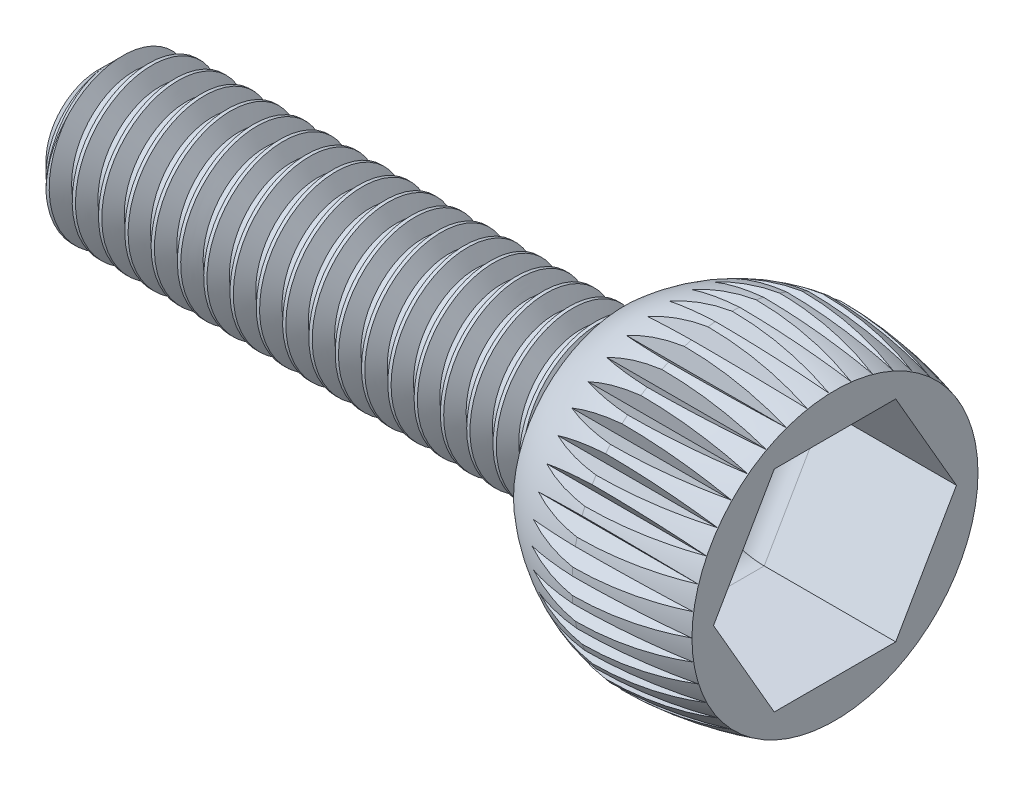
SolidWorks part; units mm, degrees
ref_plane "Front Plane" through (0, 0, 0) normal (0, 0, 1) x (1, 0, 0)
ref_plane "Top Plane" through (0, 0, 0) normal (0, 1, 0) x (1, 0, 0)
ref_plane "Right Plane" through (0, 0, 0) normal (1, 0, 0) x (0, 0, -1)
sketch "Sketch1" plane through (0, 0, 0) normal (1, 0, 0) x (0, 0, -1)
  circle A0 centre (0, 0) radius 3
  dimension "D1" = 6
extrude "Boss-Extrude1" add sketch "Sketch1" along normal blind 20
sketch "Sketch4" plane through (20, 0, 0) normal (1, 0, 0) x (0, 0, -1)
  circle A0 centre (0, 0) radius 6
  dimension "D1" = 12
extrude "Boss-Extrude2" add sketch "Sketch4" along normal blind 8
sketch "Sketch5" plane through (28, 0, 0) normal (1, 0, 0) x (0, 0, -1)
  line L0 (-5.4402, 0) -> (0, 0)
  line L1 (-5.4402, 0) -> (-5.9916, 0.3183)
  line L2 (-6.2799, 0.4848) -> (-6.2799, -0.4848)
  line L3 (-6.2799, -0.4848) -> (-6.2619, -0.4744)
  line L4 (-5.3765, 0.8305) -> (-5.8727, 1.2292)
  line L5 (-6.2803, 0.4795) -> (-6.261, 0.487)
  line L6 (-5.1867, 1.6414) -> (-5.6163, 2.1112)
  line L7 (-6.1335, 1.4326) -> (-6.1132, 1.4371)
  line L8 (-4.8754, 2.4139) -> (-5.2282, 2.9438)
  line L9 (-5.8429, 2.3521) -> (-5.8222, 2.3534)
  line L10 (-4.4497, 3.1299) -> (-4.7175, 3.7074)
  line L11 (-5.4154, 3.2164) -> (-5.3947, 3.2146)
  line L12 (-3.9198, 3.7724) -> (-4.0963, 4.3841)
  line L13 (-4.8609, 4.0054) -> (-4.8408, 4.0004)
  line L14 (-3.298, 4.3266) -> (-3.3791, 4.958)
  line L15 (-4.1925, 4.7005) -> (-4.1734, 4.6925)
  line L16 (-2.5989, 4.7793) -> (-2.5827, 5.4157)
  line L17 (-3.4259, 5.2854) -> (-3.4082, 5.2746)
  line L18 (-1.8389, 5.12) -> (-1.7257, 5.7465)
  line L19 (-2.5789, 5.7464) -> (-2.5631, 5.733)
  line L20 (-1.0358, 5.3407) -> (-0.8283, 5.9426)
  line L21 (-1.6715, 6.0727) -> (-1.6579, 6.0571)
  line L22 (-0.2084, 5.4363) -> (0.0886, 5.9993)
  line L23 (-0.7249, 6.2567) -> (-0.7139, 6.2392)
  line L24 (0.6239, 5.4044) -> (1.0033, 5.9155)
  line L25 (0.2386, 6.294) -> (0.2469, 6.275)
  line L26 (1.4416, 5.2458) -> (1.8946, 5.693)
  line L27 (1.1966, 6.1838) -> (1.2019, 6.1638)
  line L28 (2.2254, 4.9642) -> (2.7414, 5.3371)
  line L29 (2.1266, 5.9287) -> (2.1287, 5.9081)
  line L30 (2.9571, 4.5664) -> (3.524, 4.8561)
  line L31 (3.0066, 5.5346) -> (3.0056, 5.5139)
  line L32 (3.6195, 4.0614) -> (4.224, 4.2612)
  line L33 (3.8163, 5.0108) -> (3.8121, 4.9905)
  line L34 (4.1971, 3.4613) -> (4.8249, 3.5665)
  line L35 (4.5364, 4.3695) -> (4.5292, 4.3501)
  line L36 (4.6763, 2.7801) -> (5.3128, 2.7882)
  line L37 (5.1503, 3.6258) -> (5.1401, 3.6077)
  line L38 (5.0458, 2.0337) -> (5.6762, 1.9445)
  line L39 (5.6434, 2.7971) -> (5.6306, 2.7808)
  line L40 (5.2971, 1.2396) -> (5.9065, 1.0553)
  line L41 (6.0042, 1.9029) -> (5.9891, 1.8887)
  line L42 (5.4243, 0.4164) -> (5.9983, 0.1413)
  line L43 (6.2243, 0.9641) -> (6.2072, 0.9524)
  line L44 (5.4243, -0.4164) -> (5.9496, -0.776)
  line L45 (6.2986, 0.0026) -> (6.2799, -0.0063)
  line L46 (5.2971, -1.2396) -> (5.7614, -1.6751)
  line L47 (6.2251, -0.9589) -> (6.2053, -0.9649)
  line L48 (5.0458, -2.0337) -> (5.4382, -2.535)
  line L49 (6.0058, -1.8979) -> (5.9853, -1.9008)
  line L50 (4.6763, -2.7801) -> (4.9875, -3.3354)
  line L51 (5.6457, -2.7924) -> (5.625, -2.7922)
  line L52 (4.1971, -3.4613) -> (4.4199, -4.0576)
  line L53 (5.1533, -3.6215) -> (5.1328, -3.6181)
  line L54 (3.6195, -4.0614) -> (3.7487, -4.6848)
  line L55 (4.5401, -4.3657) -> (4.5204, -4.3592)
  line L56 (2.9571, -4.5664) -> (2.9896, -5.2021)
  line L57 (3.8204, -5.0076) -> (3.802, -4.9982)
  line L58 (2.2254, -4.9642) -> (2.1605, -5.5975)
  line L59 (3.0112, -5.5321) -> (2.9945, -5.52)
  line L60 (1.4416, -5.2458) -> (1.2807, -5.8617)
  line L61 (2.1315, -5.9269) -> (2.1167, -5.9124)
  line L62 (0.6239, -5.4044) -> (0.3709, -5.9885)
  line L63 (1.2018, -6.1828) -> (1.1894, -6.1662)
  line L64 (-0.2084, -5.4363) -> (-0.5476, -5.975)
  line L65 (0.2439, -6.2938) -> (0.2342, -6.2755)
  line L66 (-1.0358, -5.3407) -> (-1.4532, -5.8214)
  line L67 (-0.7197, -6.2573) -> (-0.7265, -6.2377)
  line L68 (-1.8389, -5.12) -> (-2.3248, -5.5313)
  line L69 (-1.6665, -6.0741) -> (-1.6702, -6.0537)
  line L70 (-2.5989, -4.7793) -> (-3.1419, -5.1116)
  line L71 (-2.5742, -5.7485) -> (-2.5747, -5.7278)
  line L72 (-3.298, -4.3266) -> (-3.8854, -4.5721)
  line L73 (-3.4215, -5.2882) -> (-3.4189, -5.2677)
  line L74 (-3.9198, -3.7724) -> (-4.5378, -3.9254)
  line L75 (-4.1886, -4.7039) -> (-4.1829, -4.684)
  line L76 (-4.4497, -3.1299) -> (-5.0838, -3.1867)
  line L77 (-4.8576, -4.0094) -> (-4.8489, -3.9906)
  line L78 (-4.8754, -2.4139) -> (-5.5107, -2.3733)
  line L79 (-5.4127, -3.2209) -> (-5.4012, -3.2037)
  line L80 (-5.1867, -1.6414) -> (-5.8084, -1.5043)
  line L81 (-5.8409, -2.3569) -> (-5.827, -2.3416)
  line L82 (-5.3765, -0.8305) -> (-5.9699, -0.6)
  line L83 (-6.1323, -1.4377) -> (-6.1161, -1.4247)
  line L84 (-5.5107, 2.3733) -> (-4.8754, 2.4139)
  line L85 (-5.827, 2.3416) -> (-5.8409, 2.3569)
  line L86 (-5.8084, 1.5043) -> (-5.1867, 1.6414)
  line L87 (-6.1161, 1.4247) -> (-6.1323, 1.4377)
  line L88 (-5.9699, 0.6) -> (-5.3765, 0.8305)
  line L89 (-6.2619, 0.4744) -> (-6.2799, 0.4848)
  line L90 (-5.9916, -0.3183) -> (-5.4402, 0)
  line L91 (-6.261, -0.487) -> (-6.2803, -0.4795)
  line L92 (-5.8727, -1.2292) -> (-5.3765, -0.8305)
  line L93 (-6.1132, -1.4371) -> (-6.1335, -1.4326)
  line L94 (-5.6163, -2.1112) -> (-5.1867, -1.6414)
  line L95 (-5.8222, -2.3534) -> (-5.8429, -2.3521)
  line L96 (-5.2282, -2.9438) -> (-4.8754, -2.4139)
  line L97 (-5.3947, -3.2146) -> (-5.4154, -3.2164)
  line L98 (-4.7175, -3.7074) -> (-4.4497, -3.1299)
  line L99 (-4.8408, -4.0004) -> (-4.8609, -4.0054)
  line L100 (-4.0963, -4.3841) -> (-3.9198, -3.7724)
  line L101 (-4.1734, -4.6925) -> (-4.1925, -4.7005)
  line L102 (-3.3791, -4.958) -> (-3.298, -4.3266)
  line L103 (-3.4082, -5.2746) -> (-3.4259, -5.2854)
  line L104 (-2.5827, -5.4157) -> (-2.5989, -4.7793)
  line L105 (-2.5631, -5.733) -> (-2.5789, -5.7464)
  line L106 (-1.7257, -5.7465) -> (-1.8389, -5.12)
  line L107 (-1.6579, -6.0571) -> (-1.6715, -6.0727)
  line L108 (-0.8283, -5.9426) -> (-1.0358, -5.3407)
  line L109 (-0.7139, -6.2392) -> (-0.7249, -6.2567)
  line L110 (0.0886, -5.9993) -> (-0.2084, -5.4363)
  line L111 (0.2469, -6.275) -> (0.2386, -6.294)
  line L112 (1.0033, -5.9155) -> (0.6239, -5.4044)
  line L113 (1.2019, -6.1638) -> (1.1966, -6.1838)
  line L114 (1.8946, -5.693) -> (1.4416, -5.2458)
  line L115 (2.1287, -5.9081) -> (2.1266, -5.9287)
  line L116 (2.7414, -5.3371) -> (2.2254, -4.9642)
  line L117 (3.0056, -5.5139) -> (3.0066, -5.5346)
  line L118 (3.524, -4.8561) -> (2.9571, -4.5664)
  line L119 (3.8121, -4.9905) -> (3.8163, -5.0108)
  line L120 (4.224, -4.2612) -> (3.6195, -4.0614)
  line L121 (4.5292, -4.3501) -> (4.5364, -4.3695)
  line L122 (4.8249, -3.5665) -> (4.1971, -3.4613)
  line L123 (5.1401, -3.6077) -> (5.1503, -3.6258)
  line L124 (5.3128, -2.7882) -> (4.6763, -2.7801)
  line L125 (5.6306, -2.7808) -> (5.6434, -2.7971)
  line L126 (5.6762, -1.9445) -> (5.0458, -2.0337)
  line L127 (5.9891, -1.8887) -> (6.0042, -1.9029)
  line L128 (5.9065, -1.0553) -> (5.2971, -1.2396)
  line L129 (6.2072, -0.9524) -> (6.2243, -0.9641)
  line L130 (5.9983, -0.1413) -> (5.4243, -0.4164)
  line L131 (6.2799, 0.0063) -> (6.2986, -0.0026)
  line L132 (5.9496, 0.776) -> (5.4243, 0.4164)
  line L133 (6.2053, 0.9649) -> (6.2251, 0.9589)
  line L134 (5.7614, 1.6751) -> (5.2971, 1.2396)
  line L135 (5.9853, 1.9008) -> (6.0058, 1.8979)
  line L136 (5.4382, 2.535) -> (5.0458, 2.0337)
  line L137 (5.625, 2.7922) -> (5.6457, 2.7924)
  line L138 (4.9875, 3.3354) -> (4.6763, 2.7801)
  line L139 (5.1328, 3.6181) -> (5.1533, 3.6215)
  line L140 (4.4199, 4.0576) -> (4.1971, 3.4613)
  line L141 (4.5204, 4.3592) -> (4.5401, 4.3657)
  line L142 (3.7487, 4.6848) -> (3.6195, 4.0614)
  line L143 (3.802, 4.9982) -> (3.8204, 5.0076)
  line L144 (2.9896, 5.2021) -> (2.9571, 4.5664)
  line L145 (2.9945, 5.52) -> (3.0112, 5.5321)
  line L146 (2.1605, 5.5975) -> (2.2254, 4.9642)
  line L147 (2.1167, 5.9124) -> (2.1315, 5.9269)
  line L148 (1.2807, 5.8617) -> (1.4416, 5.2458)
  line L149 (1.1894, 6.1662) -> (1.2018, 6.1828)
  line L150 (0.3709, 5.9885) -> (0.6239, 5.4044)
  line L151 (0.2342, 6.2755) -> (0.2439, 6.2938)
  line L152 (-0.5476, 5.975) -> (-0.2084, 5.4363)
  line L153 (-0.7265, 6.2377) -> (-0.7197, 6.2573)
  line L154 (-1.4532, 5.8214) -> (-1.0358, 5.3407)
  line L155 (-1.6702, 6.0537) -> (-1.6665, 6.0741)
  line L156 (-2.3248, 5.5313) -> (-1.8389, 5.12)
  line L157 (-2.5747, 5.7278) -> (-2.5742, 5.7485)
  line L158 (-3.1419, 5.1116) -> (-2.5989, 4.7793)
  line L159 (-3.4189, 5.2677) -> (-3.4215, 5.2882)
  line L160 (-3.8854, 4.5721) -> (-3.298, 4.3266)
  line L161 (-4.1829, 4.684) -> (-4.1886, 4.7039)
  line L162 (-4.8489, 3.9906) -> (-4.8576, 4.0094)
  line L163 (-4.5378, 3.9254) -> (-3.9198, 3.7724)
  line L164 (-5.4012, 3.2037) -> (-5.4127, 3.2209)
  line L165 (-5.0838, 3.1867) -> (-4.4497, 3.1299)
  circle A0 centre (0, 0) radius 5.4402
  arc A1 (-3.3791, -4.958) -> (-3.1419, -5.1116) centre (0, 0) ccw
  arc A2 (-2.5827, -5.4157) -> (-2.3248, -5.5313) centre (0, 0) ccw
  circle A3 centre (0, 0) radius 6.2799
  circle A4 centre (0, 0) radius 5.4402
  circle A5 centre (0, 0) radius 5.4402
  circle A6 centre (0, 0) radius 5.4402
  circle A7 centre (0, 0) radius 5.4402
  circle A8 centre (0, 0) radius 5.4402
  circle A9 centre (0, 0) radius 5.4402
  circle A10 centre (0, 0) radius 5.4402
  circle A11 centre (0, 0) radius 5.4402
  circle A12 centre (0, 0) radius 5.4402
  circle A13 centre (0, 0) radius 5.4402
  circle A14 centre (0, 0) radius 5.4402
  circle A15 centre (0, 0) radius 5.4402
  circle A16 centre (0, 0) radius 5.4402
  circle A17 centre (0, 0) radius 5.4402
  circle A18 centre (0, 0) radius 5.4402
  circle A19 centre (0, 0) radius 5.4402
  circle A20 centre (0, 0) radius 5.4402
  circle A21 centre (0, 0) radius 5.4402
  circle A22 centre (0, 0) radius 5.4402
  circle A23 centre (0, 0) radius 5.4402
  circle A24 centre (0, 0) radius 5.4402
  circle A25 centre (0, 0) radius 5.4402
  circle A26 centre (0, 0) radius 5.4402
  circle A27 centre (0, 0) radius 5.4402
  circle A28 centre (0, 0) radius 5.4402
  circle A29 centre (0, 0) radius 5.4402
  circle A30 centre (0, 0) radius 5.4402
  circle A31 centre (0, 0) radius 5.4402
  circle A32 centre (0, 0) radius 5.4402
  circle A33 centre (0, 0) radius 5.4402
  circle A34 centre (0, 0) radius 5.4402
  circle A35 centre (0, 0) radius 5.4402
  circle A36 centre (0, 0) radius 5.4402
  circle A37 centre (0, 0) radius 5.4402
  circle A38 centre (0, 0) radius 5.4402
  circle A39 centre (0, 0) radius 5.4402
  circle A40 centre (0, 0) radius 5.4402
  circle A41 centre (0, 0) radius 5.4402
  circle A42 centre (0, 0) radius 5.4402
  circle A43 centre (0, 0) radius 5.4402
  arc A44 (-5.5107, 2.3733) -> (-5.6163, 2.1112) centre (0, 0) ccw
  arc A45 (-5.8084, 1.5043) -> (-5.8727, 1.2292) centre (0, 0) ccw
  arc A46 (-5.9699, 0.6) -> (-5.9916, 0.3183) centre (0, 0) ccw
  arc A47 (-5.9916, -0.3183) -> (-5.9699, -0.6) centre (0, 0) ccw
  arc A48 (-1.7257, -5.7465) -> (-1.4532, -5.8214) centre (0, 0) ccw
  arc A49 (-5.8727, -1.2292) -> (-5.8084, -1.5043) centre (0, 0) ccw
  arc A50 (-5.6163, -2.1112) -> (-5.5107, -2.3733) centre (0, 0) ccw
  arc A51 (-5.2282, -2.9438) -> (-5.0838, -3.1867) centre (0, 0) ccw
  arc A52 (-4.7175, -3.7074) -> (-4.5378, -3.9254) centre (0, 0) ccw
  arc A53 (-4.0963, -4.3841) -> (-3.8854, -4.5721) centre (0, 0) ccw
  arc A54 (-0.8283, -5.9426) -> (-0.5476, -5.975) centre (0, 0) ccw
  arc A55 (0.0886, -5.9993) -> (0.3709, -5.9885) centre (0, 0) ccw
  arc A56 (1.0033, -5.9155) -> (1.2807, -5.8617) centre (0, 0) ccw
  arc A57 (1.8946, -5.693) -> (2.1605, -5.5975) centre (0, 0) ccw
  arc A58 (2.7414, -5.3371) -> (2.9896, -5.2021) centre (0, 0) ccw
  arc A59 (3.524, -4.8561) -> (3.7487, -4.6848) centre (0, 0) ccw
  arc A60 (4.224, -4.2612) -> (4.4199, -4.0576) centre (0, 0) ccw
  arc A61 (4.8249, -3.5665) -> (4.9875, -3.3354) centre (0, 0) ccw
  arc A62 (5.3128, -2.7882) -> (5.4382, -2.535) centre (0, 0) ccw
  arc A63 (5.6762, -1.9445) -> (5.7614, -1.6751) centre (0, 0) ccw
  arc A64 (5.9065, -1.0553) -> (5.9496, -0.776) centre (0, 0) ccw
  arc A65 (5.9983, -0.1413) -> (5.9983, 0.1413) centre (0, 0) ccw
  arc A66 (5.9496, 0.776) -> (5.9065, 1.0553) centre (0, 0) ccw
  arc A67 (5.7614, 1.6751) -> (5.6762, 1.9445) centre (0, 0) ccw
  arc A68 (5.4382, 2.535) -> (5.3128, 2.7882) centre (0, 0) ccw
  arc A69 (4.9875, 3.3354) -> (4.8249, 3.5665) centre (0, 0) ccw
  arc A70 (3.7487, 4.6848) -> (3.524, 4.8561) centre (0, 0) ccw
  arc A71 (2.1605, 5.5975) -> (1.8946, 5.693) centre (0, 0) ccw
  arc A72 (1.2807, 5.8617) -> (1.0033, 5.9155) centre (0, 0) ccw
  arc A73 (4.4199, 4.0576) -> (4.224, 4.2612) centre (0, 0) ccw
  arc A74 (2.9896, 5.2021) -> (2.7414, 5.3371) centre (0, 0) ccw
  arc A75 (0.3709, 5.9885) -> (0.0886, 5.9993) centre (0, 0) ccw
  arc A76 (-0.5476, 5.975) -> (-0.8283, 5.9426) centre (0, 0) ccw
  arc A77 (-2.3248, 5.5313) -> (-2.5827, 5.4157) centre (0, 0) ccw
  arc A78 (-3.1419, 5.1116) -> (-3.3791, 4.958) centre (0, 0) ccw
  arc A79 (-1.4532, 5.8214) -> (-1.7257, 5.7465) centre (0, 0) ccw
  arc A80 (-3.8854, 4.5721) -> (-4.0963, 4.3841) centre (0, 0) ccw
  arc A81 (-4.5378, 3.9254) -> (-4.7175, 3.7074) centre (0, 0) ccw
  arc A82 (-5.0838, 3.1867) -> (-5.2282, 2.9438) centre (0, 0) ccw
  point P174 (0, 0)
  circle M124 centre (0, 0) radius 6
  dimension "D1" = 10.8805
  dimension "D5" = 12
  dimension "D6" = 12.5598
  dimension "D2" = 0.9695
  dimension "D3" = 0.8396
  dimension "D4" = 41
extrude "Cut-Extrude1" cut sketch "Sketch5" against normal blind 8 contours A3 | L165 L10 M124 | L163 L12 M124 | L160 L14 M124 | L158 L16 M124 | L156 L18 M124 | L154 L20 M124 | L152 L22 M124 | L150 L24 M124 | L148 L26 M124 | L146 L28 M124 | L144 L30 M124 | L142 L32 M124 | L140 L34 M124 | L138 L36 M124 | L136 L38 M124 | L134 L40 M124 | L132 L42 M124 | L130 L44 M124 | L128 L46 M124 | L126 L48 M124 | L124 L50 M124 | L122 L52 M124 | L120 L54 M124 | L118 L56 M124 | L116 L58 M124 | L114 L60 M124 | L112 L62 M124 | L110 L64 M124 | L108 L66 M124 | L106 L68 M124 | L104 L70 M124 | L102 L72 M124 | L100 L74 M124 | L98 L76 M124 | L96 L78 M124 | L94 L80 M124 | L92 L82 M124 | L90 L1 M124 | L88 L4 M124 | L86 L6 M124 | L84 L8 M124 region at (28, 0, 5.8115) region at (28, 0.8871, 5.7434) region at (28, -0.8871, 5.7434) region at (28, 1.7535, 5.5407) region at (28, -1.7535, 5.5407) region at (28, 2.5787, 5.2081) region at (28, -2.5787, 5.2081) region at (28, 3.3435, 4.7534) region at (28, -3.3435, 4.7534) region at (28, 4.0299, 4.1873) region at (28, -4.0299, 4.1873) region at (28, 4.6219, 3.5231) region at (28, -4.6219, 3.5231) region at (28, 5.1055, 2.7763) region at (28, -5.1055, 2.7763) region at (28, 5.4695, 1.9644) region at (28, -5.4695, 1.9644) region at (28, 5.7052, 1.1065) region at (28, -5.7052, 1.1065) region at (28, 5.8073, 0.2226) region at (28, -5.8073, 0.2226) region at (28, 5.7732, -0.6665) region at (28, -5.7732, -0.6665) region at (28, 5.6038, -1.5399) region at (28, -5.6038, -1.5399) region at (28, 5.303, -2.3773) region at (28, -5.303, -2.3773) region at (28, 4.878, -3.159) region at (28, -4.878, -3.159) region at (28, 4.3386, -3.8666) region at (28, -4.3386, -3.8666) region at (28, 3.6975, -4.4835) region at (28, -3.6975, -4.4835) region at (28, 2.9698, -4.9954) region at (28, -2.9698, -4.9954) region at (28, 2.1724, -5.3902) region at (28, -2.1724, -5.3902) region at (28, 1.3242, -5.6587) region at (28, -1.3242, -5.6587) region at (28, 0.4449, -5.7945) region at (28, -0.4449, -5.7945) region at (28, 0.2307, 6.0979)
sketch "Sketch7" plane through (0, 0, 0) normal (0, 1, 0) x (1, 0, 0)
  line L1 (20, -6) -> (28, -6)
  line L2 (20, 4.224) -> (20, 6)
  line L3 (20, 6) -> (28, 6)
  line L4 (20, 6) -> (28, 6)
  line L5 (390.656, 0) -> (378.1938, 0)
  line L6 (20, 4.224) -> (20, 6)
  line L7 (28, 6) -> (20, 6)
  line L8 (28, 5.4382) -> (28, 6)
  arc A0 (24, 6) -> (28, 5.4382) centre (24, -8.5207) cw
  arc A2 (20, 4.224) -> (24, 6) centre (24.8242, -1.2486) cw
  dimension "D1" = 7.2953
  dimension "D3" = 12
  dimension "D4" = 0
revolve "Cut-Revolve1" cut sketch "Sketch7" angle 360 about L5 region at (27.0039, 0, -5.832) region at (21.0986, 0, -5.4743)
sketch "Sketch8" plane through (28, 0, 0) normal (1, 0, 0) x (0, 0, -1)
  line L1 (4.6188, 0) -> (2.3094, 4)
  line L2 (2.3094, 4) -> (-2.3094, 4)
  line L3 (-2.3094, 4) -> (-4.6188, 0)
  line L4 (-4.6188, 0) -> (-2.3094, -4)
  line L5 (-2.3094, -4) -> (2.3094, -4)
  line L6 (2.3094, -4) -> (4.6188, 0)
  circle A0 centre (0, 0) radius 4 construction
  dimension "D1" = 8
  dimension "D2" = 0.8214
extrude "Cut-Extrude2" cut sketch "Sketch8" against normal blind 6
fillet "Fillet1" radius 1 6 edges at (22, -4, 0) (22, -2, 3.4641) (22, 2, 3.4641) (22, 4, 0) (22, 2, -3.4641) (22, -2, -3.4641)
chamfer "Chamfer1" distance 1 angle 45 1 edges at (0, 0, -3)
thread "Thread2" pitch 1 method cut profile "Thread Profile2" start angle 0, offset 0, length 20, pitch 1, diameter 6
ref_plane "Plane2" through (20, 0, 3) normal (0, -1, 0) x (0, 0, 1)
sketch "Thread Profile2" plane through (20, 0, 3) normal (0, -1, 0) x (0, 0, 1)
  line L0 (0, 0) -> (0, 1) construction
  line L11 (0, 0) -> (0, 0.875)
  line L12 (0, 0.875) -> (-0.5413, 0.5625)
  line L13 (-0.5413, 0.5625) -> (-0.5413, 0.3125)
  line L15 (-0.5413, 0.3125) -> (0, 0)
  line L17 (-0.5413, 0.4375) -> (0, 0.4375) construction
  point P2 (0, 0)
  dimension "Pitch" = 1
  dimension "Profile_Angle" = 60
  dimension "Profile_Land" = 0.25
  dimension "Profile_Height" = 0.5413
